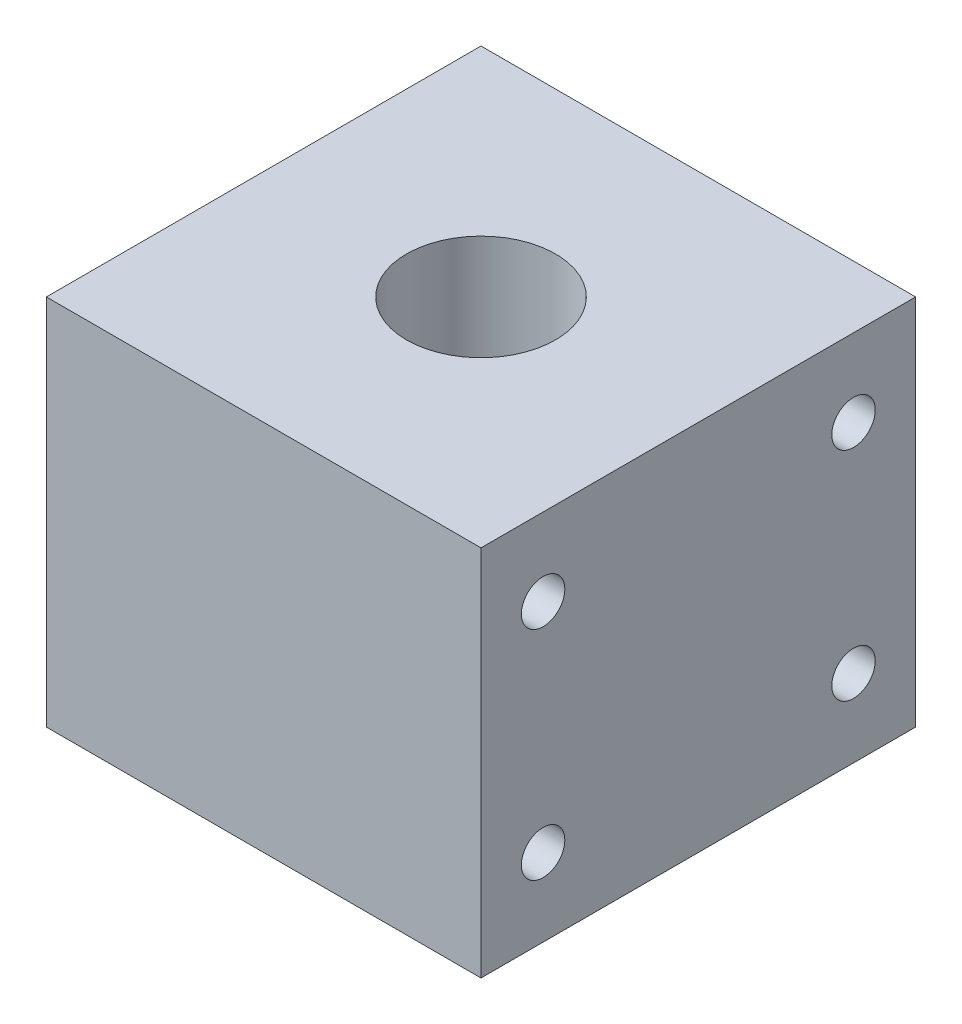
SolidWorks part; units mm, degrees
ref_plane "Płaszczyzna przednia" through (0, 0, 0) normal (0, 0, 1) x (1, 0, 0)
ref_plane "Płaszczyzna górna" through (0, 0, 0) normal (0, 1, 0) x (1, 0, 0)
ref_plane "Płaszczyzna prawa" through (0, 0, 0) normal (1, 0, 0) x (0, 0, -1)
sketch "Szkic1" plane through (0, 0, 0) normal (0, 1, 0) x (1, 0, 0)
  line L0 (0, 35) -> (70, 35) construction
  line L1 (0, 0) -> (70, 0)
  line L2 (0, 0) -> (0, 70)
  line L3 (0, 70) -> (70, 70)
  line L4 (70, 0) -> (70, 70)
  line L5 (35, 70) -> (35, 0) construction
  line L6 (5, 35) -> (5, 55)
  line L7 (15, 65) -> (55, 65)
  line L8 (65, 55) -> (65, 15)
  line L9 (55, 5) -> (15, 5)
  line L10 (5, 15) -> (5, 35)
  circle A0 centre (35, 35) radius 23.5
  arc A1 (15, 5) -> (5, 15) centre (15, 15) cw
  arc A2 (65, 15) -> (55, 5) centre (55, 15) cw
  arc A3 (55, 65) -> (65, 55) centre (55, 55) cw
  arc A4 (5, 55) -> (15, 65) centre (15, 55) cw
  circle A5 centre (35, 35) radius 20
  circle A6 centre (35, 35) radius 12
  circle A7 centre (35, 35) radius 16
  dimension "D3" = 60
  dimension "D5" = 47
  dimension "D6" = 10
  dimension "D1" = 70
  dimension "D2" = 70
  dimension "D4" = 60
extrude "Dodanie-wyciągnięcie1" add sketch "Szkic1" along normal blind 60 contours L1 L4 L3 L2 L6 A4 L7 A3 L8 A2 L9 A1 L10 | A4 L6 L10 A1 L9 A2 L8 A3 L7 A0 | A0 | A5 A6 | A7 A6 region at (0.9899, 0, -35) region at (5.8485, 0, -45) region at (12.1647, 0, -35) region at (15.5657, 0, -35) region at (19.4525, 0, -35)
extrude "Wytnij-wyciągnięcie1" cut sketch "Szkic1<3>" along normal blind 3 contours A4 L6 L10 A1 L9 A2 L8 A3 L7 A0 region at (5.8485, 0, -45)
sketch "Szkic1<3>" plane through (0, 0, 0) normal (0, 1, 0) x (1, 0, 0) same geometry as "Szkic1"
extrude "Wytnij-wyciągnięcie2" cut sketch "Szkic1<4>" along normal blind 23 contours A0 A5 | A5 A6 | A6 | A7 A6 region at (12.1647, 0, -35) region at (15.5657, 0, -35) region at (35, 0, -35) region at (19.4525, 0, -35)
sketch "Szkic1<4>" plane through (0, 0, 0) normal (0, 1, 0) x (1, 0, 0) same geometry as "Szkic1"
extrude "Wytnij-wyciągnięcie5" cut sketch "Szkic1<6>" along normal blind 40 contours A7 A6 region at (19.4525, 0, -35)
sketch "Szkic1<6>" plane through (0, 0, 0) normal (0, 1, 0) x (1, 0, 0) same geometry as "Szkic1"
chamfer "Sfazowanie1" distance 2 angle 45 1 edges at (35, 40, -23)
chamfer "Sfazowanie2" distance 2 angle 45 1 edges at (35, 3, -11.5)
sketch "Szkic2" plane through (70, 0, 0) normal (1, 0, 0) x (0, 0, -1)
  line L0 (35, 60) -> (35, 0) construction
  line L1 (0, 60) -> (70, 60) construction
  line L2 (0, 0) -> (70, 0) construction
  line L3 (70, 30) -> (0, 30) construction
  line L4 (70, 60) -> (70, 0) construction
  line L5 (0, 60) -> (0, 0) construction
  point P6 (10, 47.5)
  point P7 (10, 12.5)
  point P8 (60, 12.5)
  point P9 (60, 47.5)
  dimension "D1" = 25
  dimension "D2" = 35
hole_wizard "Otwór gwintowany M8x1.01" positions "Szkic 3D1" profile "Szkic4" tap size "M8x1.0" standard "ISO"
sketch3d "Szkic 3D1"
  point P0 (70, 47.5, -10)
  point P3 (70, 47.5, -60)
  point P6 (70, 12.5, -10)
  point P9 (70, 12.5, -60)
sketch "Szkic4" plane through (70, 47.5, -10) normal (0, 1, 0) x (0, 0, -1)
  line L0 (0, 0) -> (0, 10.103)
  line L1 (0, 10.103) -> (3.5, 8)
  line L2 (3.5, 8) -> (3.5, 0)
  line L5 (3.5, 0) -> (0, 0)
  line L10 (0, 10.103) -> (-3.5, 8) construction
  line L11 (0, -6.35) -> (0, 107.95) construction
  dimension "Średnica wiertła gwintu" = 7
  dimension "Głębokość otworu gwintowanego" = 8
  dimension "Kąt wiertła" = 118
cosmetic thread "Gwint otworu1" parameters "D1"=8, "D2"=8
cosmetic thread "Gwint otworu2" parameters "D1"=8, "D2"=8
cosmetic thread "Gwint otworu3" parameters "D1"=8, "D2"=8
cosmetic thread "Gwint otworu4" parameters "D1"=8, "D2"=8
ref_plane "Płaszczyzna1" through (35, 0, 0) normal (1, 0, 0) x (0, 0, -1)
mirror "Lustro1" about plane through (35, 0, 0) normal (1, 0, 0) of "Otwór gwintowany M8x1.01"
